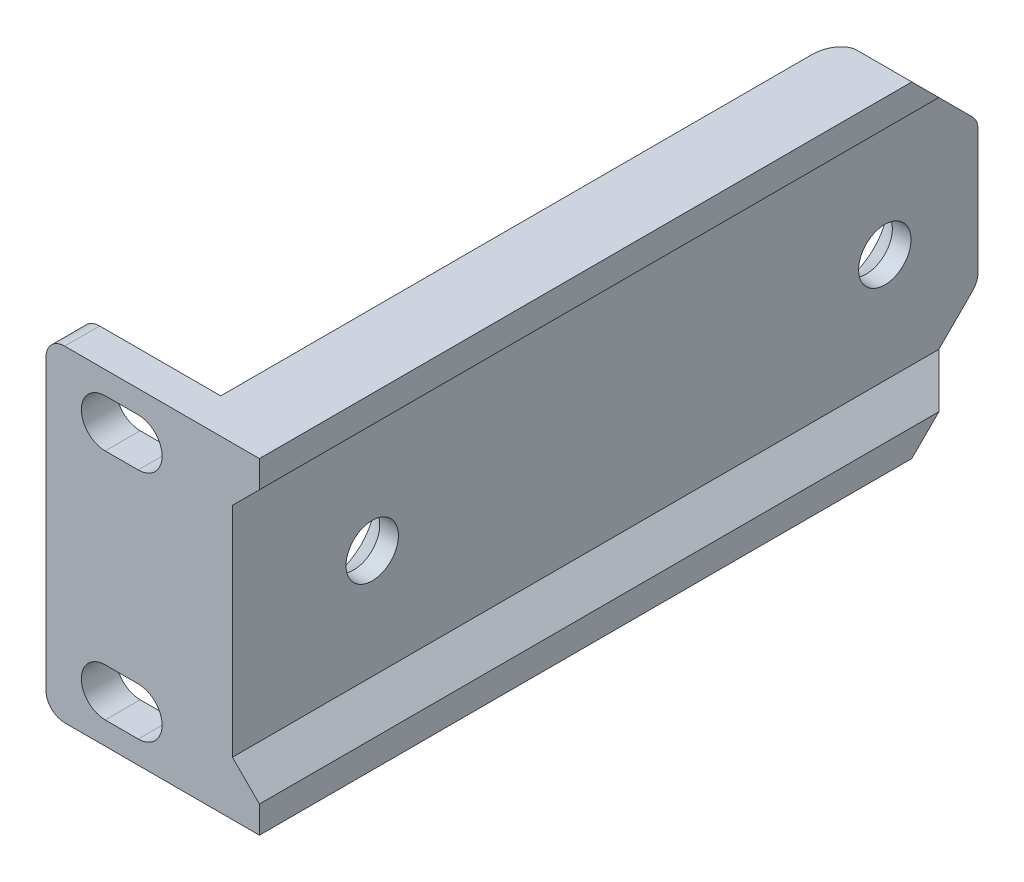
SolidWorks part; units mm, degrees
ref_plane "Plane XZ" through (0, 0, 0) normal (0, 0, 1) x (1, 0, 0)
ref_plane "Plane XY" through (0, 0, 0) normal (0, 1, 0) x (1, 0, 0)
ref_plane "Plane YZ" through (0, 0, 0) normal (1, 0, 0) x (0, 0, -1)
sketch "Sketch1" plane through (0, 0, 0) normal (0, 1, 0) x (1, 0, 0)
  line L0 (0, 0) -> (0, 101.6)
  line L1 (0, 101.6) -> (-6.35, 101.6)
  line L2 (-6.35, 101.6) -> (-6.35, 4.7625)
  line L3 (-6.35, 4.7625) -> (-25.4, 4.7625)
  line L4 (-25.4, 4.7625) -> (-25.4, 0)
  line L5 (-25.4, 0) -> (0, 0)
  dimension "D1" = 4.7625
  dimension "D2" = 6.35
  dimension "D3" = 101.6
  dimension "D4" = 25.4
extrude "Boss-Extrude1" add sketch "Sketch1" along normal mid plane 44.45
sketch "Sketch2" plane through (0, 0, 0) normal (0, 0, 1) x (1, 0, 0)
  line L1 (0, 22.225) -> (3.683, 22.225)
  line L2 (0, 22.225) -> (0, 18.542)
  line L3 (0, 18.542) -> (3.683, 18.542)
  line L4 (3.683, 22.225) -> (3.683, 18.542)
  line L5 (0, -22.225) -> (3.683, -22.225)
  line L6 (0, -22.225) -> (0, -18.542)
  line L7 (0, -18.542) -> (3.683, -18.542)
  line L8 (3.683, -22.225) -> (3.683, -18.542)
  dimension "D1" = 3.683
  dimension "D2" = 3.683
extrude "Boss-Extrude2" add sketch "Sketch2" against normal up to surface (101.6 mm away) up to face at (-3.175, 0, -101.6)
sketch "Sketch3" plane through (0, 0, 0) normal (0, 0, 1) x (1, 0, 0)
  line L0 (-17.33, 15.875) -> (-12.8324, 15.875) construction
  line L1 (-17.33, 19.1262) -> (-12.8325, 19.1262)
  line L2 (-17.33, 12.6238) -> (-12.8325, 12.6238)
  line L3 (0, 0) -> (-25.4, 0) construction
  line L4 (0, 18.542) -> (0, -18.542) construction
  line L5 (-25.4, 22.225) -> (-25.4, -22.225) construction
  line L6 (-17.33, -15.875) -> (-12.8324, -15.875) construction
  line L7 (-17.33, -19.1262) -> (-12.8325, -19.1262)
  line L8 (-17.33, -12.6238) -> (-12.8325, -12.6238)
  line L9 (-17.33, 15.875) -> (-20.5812, 15.875) construction
  line L10 (-12.8324, 15.875) -> (-9.5812, 15.875) construction
  arc A0 (-17.33, 19.1262) -> (-17.33, 12.6238) centre (-17.33, 15.875) ccw
  arc A1 (-12.8325, 12.6238) -> (-12.8325, 19.1262) centre (-12.8324, 15.875) ccw
  arc A2 (-17.33, -19.1262) -> (-17.33, -12.6238) centre (-17.33, -15.875) cw
  arc A3 (-12.8325, -12.6238) -> (-12.8325, -19.1262) centre (-12.8324, -15.875) cw
  point P2 (-15.0812, 15.875)
  point P15 (-15.0812, -15.875)
  dimension "D1" = 11
  dimension "D2" = 6.5024
  dimension "D3" = 15.0812
  dimension "D4" = 15.875
extrude "Cut-Extrude1" cut sketch "Sketch3" against normal through all
fillet "Fillet1" radius 2.54 2 edges at (-25.4, -22.225, -2.3813) (-25.4, 22.225, -2.3813)
hole_wizard "CSK for 1/4 Flat Head Machine Screw1" positions "Sketch4" profile "Sketch5" countersink size "1/4" standard "ANSI Inch" end condition through all
sketch "Sketch4" plane through (-6.35, 0, 0) normal (-1, 0, 0) x (0, 0, 1)
  line L0 (0, 18.542) -> (0, -18.542) construction
  line L1 (-88.9, 0) -> (-19.05, 0) construction
  line L2 (-19.05, 0) -> (0, 0) construction
  point P0 (-19.05, 0)
  point P2 (-88.9, 0)
  dimension "D1" = 19.05
  dimension "D2" = 88.9
sketch "Sketch5" plane through (-6.35, 0, -19.05) normal (0, 1, 0) x (0, 0, 1)
  line L0 (0, 0) -> (0, 10.033)
  line L1 (0, 10.033) -> (3.5712, 10.033)
  line L2 (3.5712, 10.033) -> (3.5712, 3.8069)
  line L3 (3.5712, 3.8069) -> (6.8805, 0)
  line L5 (6.8805, 0) -> (0, 0)
  line L6 (-3.5712, 3.8069) -> (-6.8805, 0) construction
  line L11 (0, -6.35) -> (0, 107.95) construction
  dimension "Thru Hole Dia." = 7.1425
  dimension "Thru Hole Depth" = 10.033
  dimension "Near C'Sink Dia." = 13.761
  dimension "Near C'Sink Angle" = 82
sketch "Sketch6" plane through (-6.35, 0, 0) normal (-1, 0, 0) x (0, 0, 1)
  line L0 (-101.6, 22.225) -> (-88.9, 22.225)
  line L1 (-101.6, 22.225) -> (-4.7625, 22.225) construction
  line L2 (-88.9, 22.225) -> (-101.6, 9.525)
  line L3 (-101.6, 22.225) -> (-101.6, -22.225) construction
  line L4 (-101.6, 9.525) -> (-101.6, 22.225)
  line L5 (-101.6, 0) -> (0, 0) construction
  line L6 (-88.9, -22.225) -> (-101.6, -9.525)
  line L7 (-101.6, -22.225) -> (-88.9, -22.225)
  line L8 (-101.6, -9.525) -> (-101.6, -22.225)
  dimension "D1" = 12.7
extrude "Cut-Extrude2" cut sketch "Sketch6" against normal through all
fillet "Fillet2" radius 2.54 5 edges at (-6.35, 15.875, -95.25) (-3.175, 9.525, -101.6) (-6.35, -15.875, -95.25) (-3.175, -9.525, -101.6) (-6.35, 0, -101.6)
chamfer "Chamfer1" distance 3.683 angle 45 2 edges at (0, -18.542, -46.2915) (0, 18.542, -46.2915)
